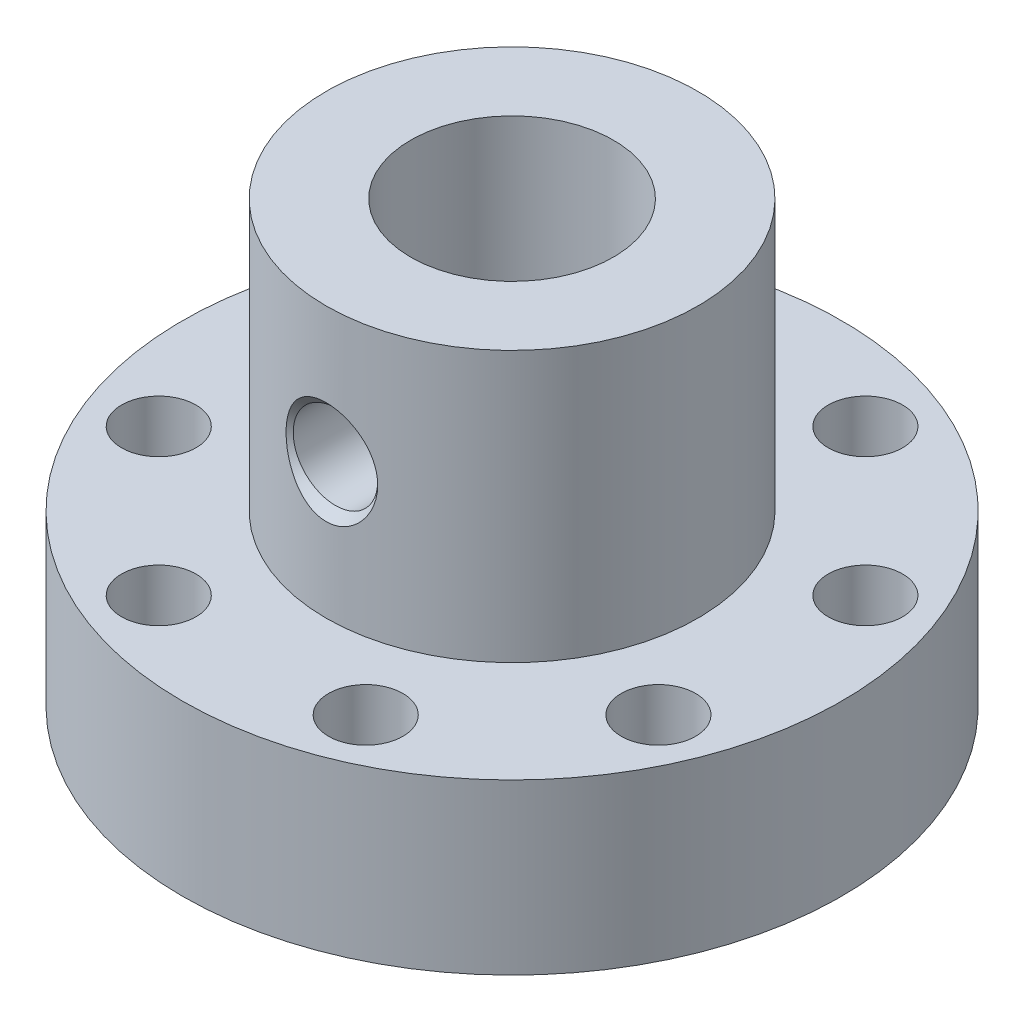
SolidWorks part; units mm, degrees
ref_plane "Front Plane" through (0, 0, 0) normal (0, 0, 1) x (1, 0, 0)
ref_plane "Top Plane" through (0, 0, 0) normal (0, 1, 0) x (1, 0, 0)
ref_plane "Right Plane" through (0, 0, 0) normal (1, 0, 0) x (0, 0, -1)
sketch "Sketch2" plane through (0, 0, 0) normal (0, 1, 0) x (1, 0, 0)
  circle A0 centre (0, 0) radius 9.75
  circle A1 centre (0, 0) radius 4
  dimension "D1" = 19.5
  dimension "D2" = 8
extrude "Boss-Extrude1" add sketch "Sketch2" along normal blind 3
sketch "Sketch3" plane through (0, 3, 0) normal (0, 1, 0) x (1, 0, 0)
  circle A0 centre (0, 0) radius 3
  circle A1 centre (0, 0) radius 5.5
  point P3 (8.4359, 1.6256)
  dimension "D1" = 6
  dimension "D2" = 11
extrude "Boss-Extrude2" add sketch "Sketch3" along normal blind 10
sketch "Sketch16" plane through (0, 3, 0) normal (0, 1, 0) x (1, 0, 0)
  circle A0 centre (0, 0) radius 9.75
  circle A1 centre (0, 0) radius 5.5
  point P3 (1.1603, 0.6666)
  dimension "D1" = 19.5
  dimension "D2" = 11
extrude "Boss-Extrude3" add sketch "Sketch16" along normal blind 2
sketch "Sketch5" plane through (0, 5, 0) normal (0, 1, 0) x (1, 0, 0)
  circle A2 centre (3.0615, 7.391) radius 1.1
  circle A3 centre (7.391, 3.0615) radius 1.1
  circle A4 centre (7.391, -3.0615) radius 1.1
  circle A5 centre (3.0615, -7.391) radius 1.1
  circle A6 centre (-3.0615, -7.391) radius 1.1
  circle A7 centre (-7.391, -3.0615) radius 1.1
  circle A8 centre (-7.391, 3.0615) radius 1.1
  circle A9 centre (-3.0615, 7.391) radius 1.1
  point P0 (2.9813, 7.4237)
  point P11 (0, 0)
  point P20 (0, 0)
  dimension "D4" = 8
  dimension "D1" = 2.2
  dimension "D2" = 8
ref_plane "Plane1" through (0, 0, 5.5) normal (0, 0, 1) x (1, 0, 0)
sketch "Sketch12" plane through (0, 0, 5.5) normal (0, 0, 1) x (1, 0, 0)
  line L0 (5.5, 13) -> (-5.5, 13) construction
  point P0 (0, 9)
  point P1 (0, 0)
  dimension "D1" = 4
hole_wizard "M3x0.5 Tapped Hole1" positions "Sketch13" profile "Sketch15" tap size "M3x0.5" standard "ANSI Metric" end condition up to next
sketch "Sketch13" plane through (0, 0, 5.5) normal (0, 0, 1) x (1, 0, 0)
  point P0 (0, 9)
sketch "Sketch15" plane through (0, 9, 5.5) normal (1, 0, 0) x (0, -1, 0)
  line L0 (0, 0) -> (0, 2.5)
  line L1 (0, 2.5) -> (1.25, 2.5)
  line L2 (1.25, 2.5) -> (1.25, 0.275)
  line L3 (1.25, 0.275) -> (1.525, 0)
  line L5 (1.525, 0) -> (0, 0)
  line L6 (-1.25, 0.275) -> (-1.525, 0) construction
  line L11 (0, -6.35) -> (0, 107.95) construction
  dimension "Thru Tap Drill Dia." = 2.5
  dimension "Thru Tap Drill Depth" = 2.5
  dimension "Near C'Sink Dia." = 3.05
  dimension "Near C'Sink Angle" = 90
cosmetic thread "Hole Thread9" parameters "D2"=3
extrude "Cut-Extrude1" cut sketch "Sketch5" against normal through all
